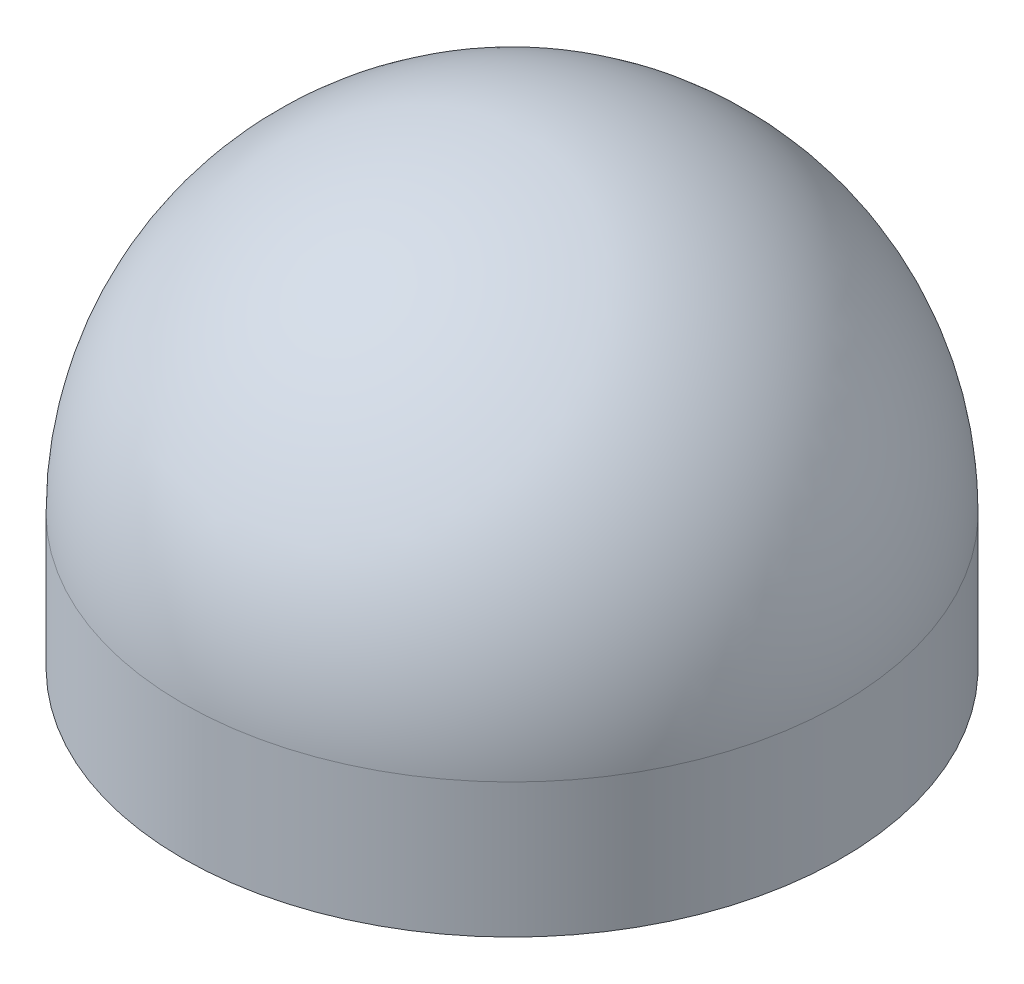
SolidWorks part; units mm, degrees
ref_plane "前视基准面" through (0, 0, 0) normal (0, 0, 1) x (1, 0, 0)
ref_plane "上视基准面" through (0, 0, 0) normal (0, 1, 0) x (1, 0, 0)
ref_plane "右视基准面" through (0, 0, 0) normal (1, 0, 0) x (0, 0, -1)
other "Configuration Table"
sketch "草图1" plane through (0, 0, 0) normal (0, 1, 0) x (1, 0, 0)
  line L0 (0, 2.1) -> (0, -2.1)
  arc A0 (0, -2.1) -> (0, 2.1) centre (0, 0) ccw
  dimension "D1" = 4.2
revolve "旋转1" add sketch "草图1" angle 180 about L0
sketch "草图6" plane through (0, 0, 0) normal (1, 0, 0) x (0, 0, -1)
  line L1 (0, 0) -> (2.0995, 0)
  line L2 (0, 0) -> (0, -0.8562)
  line L3 (0, -0.8562) -> (2.0995, -0.8562)
  line L4 (2.0995, 0) -> (2.0995, -0.8562)
revolve "旋转2" add sketch "草图6" angle 360 about L2
sketch "草图7" plane through (0, 0, 0) normal (1, 0, 0) x (0, 0, -1)
  line L0 (-2.0995, -0.8562) -> (2.0995, -0.8562) construction
  line L1 (0, -0.1037) -> (2.0505, -0.1037)
  line L2 (0, -0.1037) -> (0, -0.8562)
  line L3 (0, -0.8562) -> (2.0505, -0.8562)
  line L4 (2.0505, -0.1037) -> (2.0505, -0.8562)
revolve "切除-旋转2" cut sketch "草图7" angle 360 about L2
